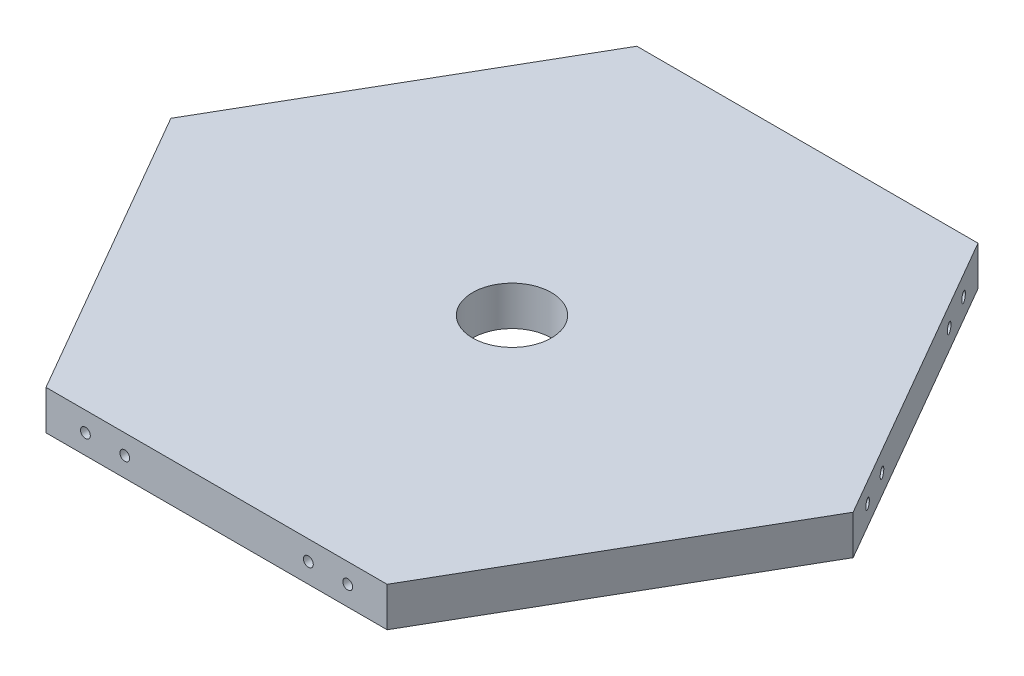
SolidWorks part; units mm, degrees
ref_plane "Front Plane" through (0, 0, 0) normal (0, 0, 1) x (1, 0, 0)
ref_plane "Top Plane" through (0, 0, 0) normal (0, 1, 0) x (1, 0, 0)
ref_plane "Right Plane" through (0, 0, 0) normal (1, 0, 0) x (0, 0, -1)
sketch "Sketch1" plane through (0, 0, 0) normal (0, 1, 0) x (1, 0, 0)
  line L7 (-43.3013, -75) -> (43.3013, -75)
  line L8 (43.3013, -75) -> (86.6025, 0)
  line L9 (86.6025, 0) -> (43.3013, 75)
  line L10 (43.3013, 75) -> (-43.3013, 75)
  line L11 (-43.3013, 75) -> (-86.6025, 0)
  line L12 (-86.6025, 0) -> (-43.3013, -75)
  circle A0 centre (0, 0) radius 75 construction
  dimension "D1" = 150
extrude "Boss-Extrude1" add sketch "Sketch1" along normal blind 10
sketch "Sketch2" plane through (0, 0, 75) normal (0, 0, 1) x (1, 0, 0)
  line L0 (-43.3013, 10) -> (-43.3013, 0) construction
  line L1 (-43.3013, 0) -> (43.3013, 0) construction
  line L2 (0, 0) -> (0, 21.4355) construction
  circle A0 centre (-33.3013, 5) radius 1.25
  circle A1 centre (-23.3013, 5) radius 1.25
  circle A2 centre (23.3013, 5) radius 1.25
  circle A3 centre (33.3013, 5) radius 1.25
  dimension "D1" = 2.5
  dimension "D2" = 10
  dimension "D3" = 10
  dimension "D4" = 5
extrude "Cut-Extrude1" cut sketch "Sketch2" against normal blind 10
sketch "Sketch3" plane through (0, 10, 0) normal (0, 1, 0) x (1, 0, 0)
  circle A0 centre (0, 0) radius 10
  dimension "D1" = 20
extrude "Cut-Extrude2" cut sketch "Sketch3" against normal through all
pattern_circular "CirPattern1" count 3 over 360 about axis through (0, 0, 0) along (0, 1, 0) of "Cut-Extrude1" reverse direction yes
sketch "Sketch5" plane through (0, 10, 0) normal (0, 1, 0) x (1, 0, 0)
  line L0 (0, 0) -> (86.6025, 0) construction
  line L1 (86.6025, 0) -> (79.1025, 12.9904)
  line L2 (86.6025, 0) -> (43.3013, 75) construction
  line L3 (0, 0) -> (79.1025, 12.9904)
  line L4 (43.3013, 75) -> (50.8013, 62.0096)
  line L5 (-43.3013, 75) -> (-50.8013, 62.0096)
  line L6 (-43.3013, 75) -> (-86.6025, 0) construction
  line L7 (-86.6025, 0) -> (-79.1025, 12.9904)
  line L8 (-43.3013, -75) -> (-28.3013, -75)
  line L9 (-43.3013, -75) -> (43.3013, -75) construction
  line L10 (43.3013, -75) -> (28.3013, -75)
  line L11 (0, 0) -> (50.8013, 62.0096)
  line L12 (0, 0) -> (-50.8013, 62.0096)
  line L13 (0, 0) -> (-79.1025, 12.9904)
  line L14 (0, 0) -> (-28.3013, -75)
  line L15 (0, 0) -> (28.3013, -75)
  line L16 (0, 0) -> (-64.9519, 37.5)
  line L17 (0, 0) -> (64.9519, 37.5)
  line L18 (0, 0) -> (0, -75)
  dimension "D1" = 15
  dimension "D2" = 15
  dimension "D3" = 15
  dimension "D4" = 15
  dimension "D5" = 15
  dimension "D6" = 15
  dimension "D7" = 9.326
  dimension "D8" = 50.674
  dimension "D9" = 129.326
  dimension "D10" = 170.674
  dimension "D11" = 249.326
  dimension "D12" = 290.674
  dimension "D13" = 80.1621
  dimension "D14" = 80.1621
  dimension "D15" = 80.1621
  dimension "D16" = 30
  dimension "D17" = 90
  dimension "D18" = 210
  dimension "D19" = 330
